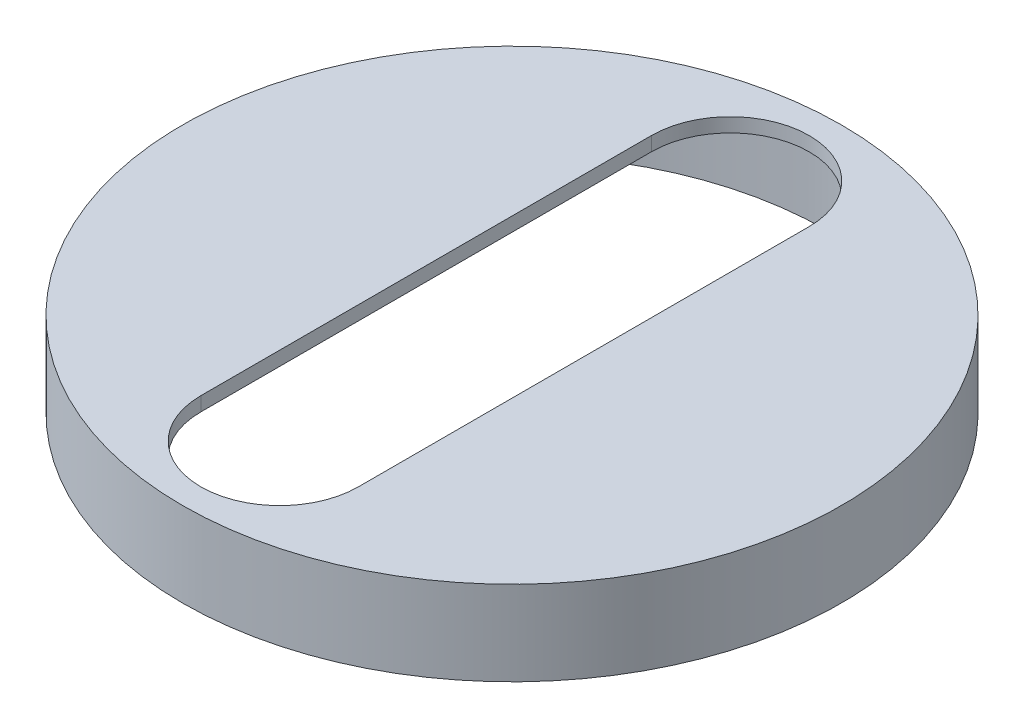
SolidWorks part; units mm, degrees
ref_plane "Front Plane" through (0, 0, 0) normal (0, 0, 1) x (1, 0, 0)
ref_plane "Top Plane" through (0, 0, 0) normal (0, 1, 0) x (1, 0, 0)
ref_plane "Right Plane" through (0, 0, 0) normal (1, 0, 0) x (0, 0, -1)
sketch "Sketch1" plane through (0, 0, 0) normal (0, 1, 0) x (1, 0, 0)
  line L3 (51, 160) -> (51, -160)
  line L4 (-61, -160) -> (-61, 160)
  circle A0 centre (0, 0) radius 224
  arc A1 (-61, -160) -> (51, -160) centre (-5, -160) ccw
  arc A2 (51, 160) -> (-61, 160) centre (-5, 160) ccw
  circle A3 centre (0, 0) radius 234
  dimension "D1" = 10
  dimension "D2" = 448
extrude "Boss-Extrude1" add sketch "Sketch1" against normal blind 60 contours A3 A0 region at (-227.3815, 0, 0)
extrude "Boss-Extrude2" add sketch "Sketch1<3>" against normal blind 10 contours A0 A2 L3 A1 L4 region at (-217.6643, 0, 0)
sketch "Sketch1<3>" plane through (0, 0, 0) normal (0, 1, 0) x (1, 0, 0) same geometry as "Sketch1"
